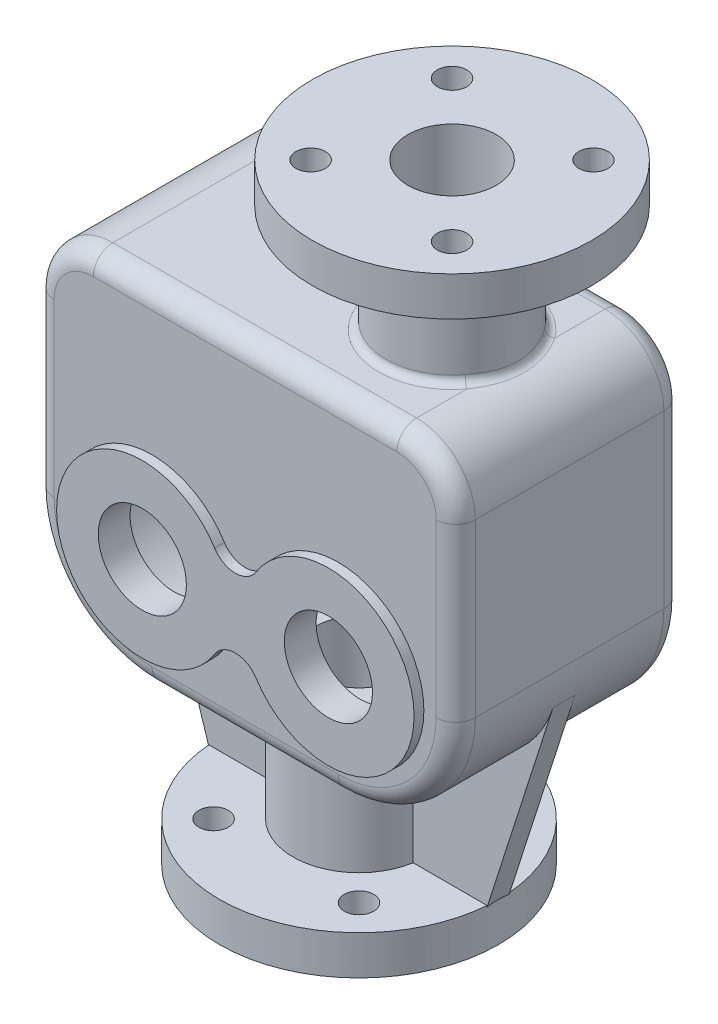
SolidWorks part; units mm, degrees
ref_plane "前基準面" through (0, 0, 0) normal (0, 0, 1) x (1, 0, 0)
ref_plane "上基準面" through (0, 0, 0) normal (0, 1, 0) x (1, 0, 0)
ref_plane "右基準面" through (0, 0, 0) normal (1, 0, 0) x (0, 0, -1)
sketch "草圖1" plane through (0, 0, 0) normal (0, 0, 1) x (1, 0, 0)
  line L0 (0, 0) -> (0, 152.9013) construction
  line L1 (-38, 0) -> (38, 0)
  line L2 (86, 48) -> (86, 118)
  line L3 (62, 142) -> (-62, 142)
  line L4 (-86, 48) -> (-86, 118)
  arc A0 (38, 0) -> (86, 48) centre (38, 48) ccw
  arc A1 (86, 118) -> (62, 142) centre (62, 118) ccw
  arc A2 (-86, 118) -> (-62, 142) centre (-62, 118) cw
  arc A3 (-38, 0) -> (-86, 48) centre (-38, 48) cw
  point P16 (0, 142)
  dimension "D1" = 48
  dimension "D2" = 24
  dimension "D3" = 94
  dimension "D4" = 172
extrude "伸長1" add sketch "草圖1" along normal mid plane 93
fillet "圓角1" radius 8 16 edges at (78.9706, 134.9706, 46.5) (86, 83, 46.5) (71.9411, 14.0589, 46.5) (0, 0, 46.5) (-71.9411, 14.0589, 46.5) (-86, 83, 46.5) (-78.9706, 134.9706, 46.5) (78.9706, 134.9706, -46.5) (86, 83, -46.5) (71.9411, 14.0589, -46.5) (0, 0, -46.5) (-71.9411, 14.0589, -46.5) (-86, 83, -46.5) (-78.9706, 134.9706, -46.5) (0, 142, 46.5) (0, 142, -46.5)
shell "薄殼1" thickness 9
fillet "圓角2" radius 3 16 edges at (0, 9, 37.5) (65.5772, 20.4228, 37.5) (77, 83, 37.5) (72.6066, 128.6066, 37.5) (0, 133, 37.5) (-72.6066, 128.6066, 37.5) (-77, 83, 37.5) (0, 9, -37.5) (65.5772, 20.4228, -37.5) (77, 83, -37.5) (72.6066, 128.6066, -37.5) (0, 133, -37.5) (-72.6066, 128.6066, -37.5) (-77, 83, -37.5) (-65.5772, 20.4228, 37.5) (-65.5772, 20.4228, -37.5)
sketch "草圖2" plane through (0, 0, 46.5) normal (0, 0, 1) x (1, 0, 0)
  line L0 (0, 0) -> (0, 98.806) construction
  arc A0 (8.4444, 29.2525) -> (8.4444, 66.7475) centre (38, 48) ccw
  arc A1 (38, 0) -> (86, 48) centre (38, 48) ccw construction
  arc A2 (-8.4444, 29.2525) -> (-8.4444, 66.7475) centre (-38, 48) cw
  arc A3 (-8.4444, 66.7475) -> (8.4444, 66.7475) centre (0, 72.1039) ccw
  arc A4 (8.4444, 29.2525) -> (-8.4444, 29.2525) centre (0, 23.8961) ccw
  dimension "D1" = 70
  dimension "D2" = 10
extrude "伸長2" add sketch "草圖2" along normal blind 4
sketch "草圖3" plane through (0, 0, 50.5) normal (0, 0, 1) x (1, 0, 0)
  circle A0 centre (38, 48) radius 18
  circle A1 centre (-38, 48) radius 18
  dimension "D1" = 36
extrude "除料-伸長1" cut sketch "草圖3" against normal up to next
sketch "草圖4" plane through (0, 0, -46.5) normal (0, 0, -1) x (-1, 0, 0)
  circle A0 centre (-38, 48) radius 27.5
  circle A1 centre (38, 48) radius 27.5
  dimension "D1" = 55
extrude "除料-伸長2" cut sketch "草圖4" against normal up to next
sketch "草圖5" plane through (0, 0, 0) normal (0, 0, 1) x (1, 0, 0)
  line L0 (0, 0) -> (0, -78.7491) construction
  line L1 (0, -66) -> (57, -66)
  line L2 (57, -66) -> (57, -50)
  line L3 (57, -50) -> (27, -50)
  line L4 (27, -50) -> (27, 0)
  line L5 (38, 0) -> (-38, 0) construction
  line L6 (27, 0) -> (0, 0)
  line L7 (0, 0) -> (0, -66)
  circle A0 centre (38, 48) radius 18 construction
  dimension "D1" = 16
  dimension "D2" = 114
  dimension "D3" = 54
  dimension "D4" = 114
revolve "旋轉1" add sketch "草圖5" angle 360 about L0
sketch "草圖6" plane through (0, 0, 0) normal (0, 0, 1) x (1, 0, 0)
  line L0 (38, 124.7535) -> (38, 229.4053) construction
  line L1 (11, 133) -> (11, 186)
  line L2 (62, 133) -> (-62, 133) construction
  line L3 (11, 186) -> (-19, 186)
  line L4 (-19, 186) -> (-19, 202)
  line L5 (-19, 202) -> (38, 202)
  line L6 (38, 202) -> (38, 133)
  line L7 (38, 133) -> (11, 133)
  line L8 (-57, -66) -> (57, -66) construction
  dimension "D1" = 54
  dimension "D2" = 114
  dimension "D3" = 16
  dimension "D4" = 268
  dimension "D5" = 38
revolve "旋轉2" add sketch "草圖6" angle 360 about L0
sketch "草圖7" plane through (0, -66, 0) normal (0, -1, 0) x (1, 0, 0)
  circle A0 centre (0, 0) radius 18
  dimension "D1" = 36
extrude "除料-伸長3" cut sketch "草圖7" against normal up to next
sketch "草圖8" plane through (0, 202, 0) normal (0, 1, 0) x (-1, 0, 0)
  circle A0 centre (-38, 0) radius 18
  dimension "D1" = 36
extrude "除料-伸長4" cut sketch "草圖8" against normal up to next
sketch "草圖9" plane through (0, -66, 0) normal (0, -1, 0) x (1, 0, 0)
  line L0 (0, 0) -> (46.395, 0) construction
  line L1 (0, 0) -> (35.2854, 35.2854) construction
  line L2 (0, 0) -> (0, 2.9334) construction
  line L3 (0, 33.6533) -> (0, -29.1078) construction
  circle A0 centre (0, 0) radius 42 construction
  circle A1 centre (29.6985, 29.6985) radius 6
  circle A2 centre (-29.6985, 29.6985) radius 6
  circle A3 centre (29.6985, -29.6985) radius 6
  circle A4 centre (-29.6985, -29.6985) radius 6
  dimension "D1" = 12
  dimension "D3" = 84
  dimension "D2" = 45
extrude "除料-伸長5" cut sketch "草圖9" against normal up to next
sketch "草圖17" plane through (0, 202, 0) normal (0, 1, 0) x (1, 0, 0)
  line L0 (38, -34.5) -> (38, 34.5) construction
  line L1 (38, 0) -> (47.2335, -3.8313) construction
  line L2 (85.5011, 0) -> (38, 0) construction
  line L3 (38, 0) -> (38, 62.5607) construction
  line L4 (38, 0) -> (70.9327, 32.9327) construction
  circle A0 centre (38, 0) radius 40.8399 construction
  circle A1 centre (66.8782, 28.8782) radius 6
  circle A2 centre (9.1218, 28.8782) radius 6
  circle A3 centre (66.8782, -28.8782) radius 6
  circle A4 centre (9.1218, -28.8782) radius 6
  dimension "D2" = 12
  dimension "D1" = 45
extrude "除料-伸長11" cut sketch "草圖17" against normal up to next
sketch "草圖18" plane through (0, 0, 0) normal (0, 0, 1) x (1, 0, 0)
  line L0 (57, -50) -> (83.7104, 33.352)
  line L1 (0, -2.7759) -> (0, -88.2241) construction
  line L2 (57.1774, -45.5) -> (10.7043, -45.5) construction
  line L4 (57, -50) -> (57, -41) construction
  arc A0 (38, 0) -> (86, 48) centre (38, 48) ccw construction
  circle A1 centre (0, -45.5) radius 57.1774 construction
  dimension "D1" = 9
rib "肋材1" sketch "草圖18" sketch "草圖18" thickness 9 extrusion direction parallel to sketch draft on no parameters "D1"=9
fillet "圓角7" radius 3 2 edges at (64.7205, 141.8453, 3.8749) (11, 142, 0)
mirror "鏡射1" about plane through (0, 0, 0) normal (1, 0, 0) of "肋材1"
